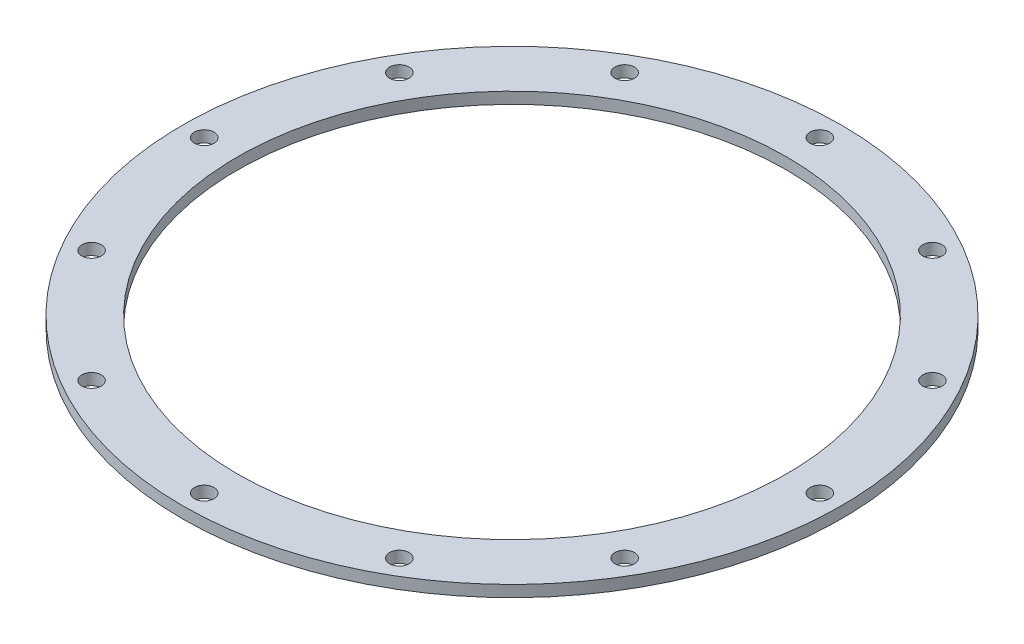
SolidWorks part; units mm, degrees
material "PTFE (general)"
ref_plane "Front Plane" through (0, 0, 0) normal (0, 0, 1) x (1, 0, 0)
ref_plane "Top Plane" through (0, 0, 0) normal (0, 1, 0) x (1, 0, 0)
ref_plane "Right Plane" through (0, 0, 0) normal (1, 0, 0) x (0, 0, -1)
ref_axis "Axis1" through (0, 55, 0) along (0, -1, 0)
sketch "Sketch1" plane through (0, 0, 0) normal (0, 0, 1) x (1, 0, 0)
  line L0 (-38.1, 0) -> (0, 0) construction
  line L1 (-38.1, 0) -> (-45.72, 0)
  line L2 (-38.1, 0) -> (-38.1, 1.5875)
  line L3 (-38.1, 1.5875) -> (-45.72, 1.5875)
  line L4 (-45.72, 0) -> (-45.72, 1.5875)
  line L7 (0, 1.5875) -> (-38.1, 1.5875) construction
  point P12 (-45.72, 0)
  point P18 (-38.1, 1.5875)
revolve "Main" add sketch "Sketch1" angle 360 about axis through (0, 55, 0) along (0, -1, 0)
sketch "Hole Location" plane through (0, 0, 0) normal (0, 1, 0) x (1, 0, 0)
  line L0 (0, 0) -> (-42.7006, 0) construction
  circle A0 centre (0, 0) radius 42.7006 construction
  dimension "D1" = 85.4012
hole_wizard "#36 (0.1065) Diameter Hole1" positions "Sketch3" profile "Sketch5" hole size "#36" standard "ANSI Inch" end condition through all
sketch "Sketch3" plane through (0, 0, 0) normal (0, -1, 0) x (-1, 0, 0)
  point P0 (42.7006, 0)
sketch "Sketch5" plane through (-42.7006, 0, 0) normal (1, 0, 0) x (0, 0, -1)
  line L0 (0, 0) -> (0, 1.5875)
  line L1 (0, 1.5875) -> (1.3525, 1.5875)
  line L2 (1.3525, 1.5875) -> (1.3525, 0)
  line L5 (1.3525, 0) -> (0, 0)
  line L11 (0, -6.35) -> (0, 107.95) construction
  dimension "Thru Hole Dia." = 2.7051
  dimension "Thru Hole Depth" = 1.5875
pattern_circular "Screw Passthroughs" count 12 over 360 about axis through (0, 55, 0) along (0, -1, 0) of "#36 (0.1065) Diameter Hole1"
equation "\"D1@Hole Location\"=\"TANK DIAMETER@Cryo Tank.Assembly\"+\"GASKET SEAT THICKNESS@Cryo Tank.Assembly\"+\"LINER THICKNESS@Cryo Tank.Assembly\"+\"ALUMINUM LAP THICKNESS@Cryo Tank.Assembly\""
